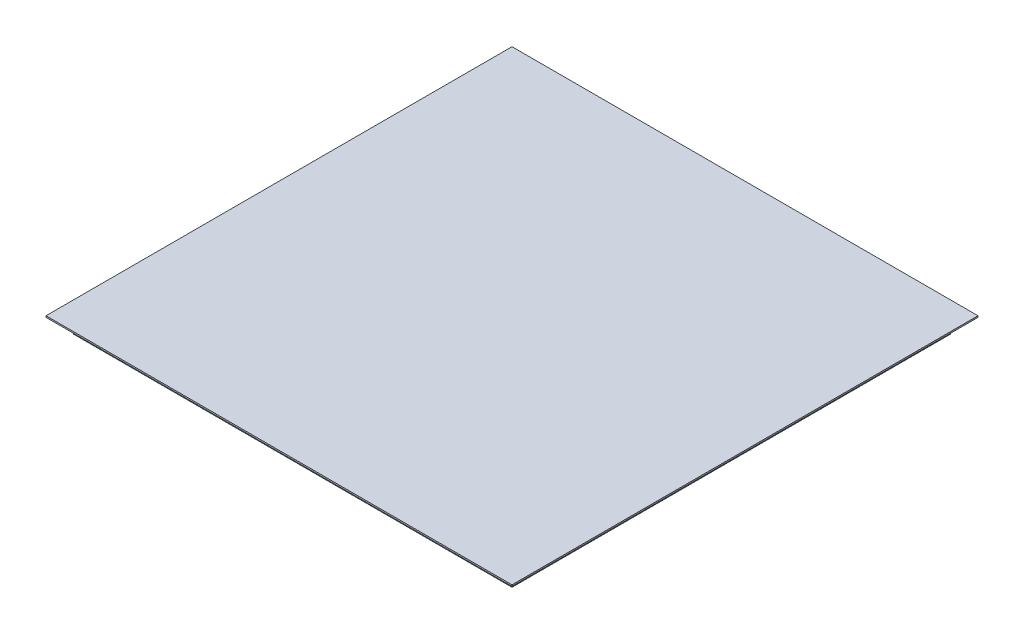
SolidWorks part; units mm, degrees
ref_plane "前视基准面" through (0, 0, 0) normal (0, 0, 1) x (1, 0, 0)
ref_plane "上视基准面" through (0, 0, 0) normal (0, 1, 0) x (1, 0, 0)
ref_plane "右视基准面" through (0, 0, 0) normal (1, 0, 0) x (0, 0, -1)
sketch "草图1" plane through (0, 0, 0) normal (0, 1, 0) x (1, 0, 0)
  line L1 (-320, -320) -> (320, -320)
  line L2 (-320, -320) -> (-320, 320)
  line L3 (-320, 320) -> (320, 320)
  line L4 (320, -320) -> (320, 320)
  line L5 (-320, -320) -> (320, 320) construction
  line L6 (-320, 320) -> (320, -320) construction
  point P0 (0, 0)
  dimension "D1" = 640
  dimension "D2" = 640
extrude "凸台-拉伸1" add sketch "草图1" along normal blind 2
sketch "草图2" plane through (0, 0, 0) normal (0, -1, 0) x (1, 0, 0)
  line L0 (299, 297.5858) -> (2.4142, 1)
  line L1 (-320, 0) -> (320, 0) construction
  line L2 (-320, -320) -> (-320, 320) construction
  line L3 (320, 320) -> (320, -320) construction
  line L4 (0, 320) -> (0, -320) construction
  line L5 (-320, 320) -> (320, 320) construction
  line L6 (320, -320) -> (-320, -320) construction
  line L7 (1, 1) -> (299, 1)
  line L8 (-300, -300) -> (300, -300) construction
  line L9 (-300, -300) -> (-300, 300) construction
  line L10 (-300, 300) -> (300, 300) construction
  line L11 (300, -300) -> (300, 300) construction
  line L12 (-300, -300) -> (300, 300) construction
  line L13 (-300, 300) -> (300, -300) construction
  line L16 (-299, 299) -> (299, 299)
  line L18 (-299, -299) -> (299, 299) construction
  line L19 (-299, 299) -> (299, -299) construction
  line L20 (-301, -301) -> (301, -301)
  line L21 (-301, -301) -> (-301, 301)
  line L22 (-301, 301) -> (301, 301)
  line L23 (301, -301) -> (301, 301)
  line L24 (-301, -301) -> (301, 301) construction
  line L25 (-301, 301) -> (301, -301) construction
  line L26 (1, -1) -> (299, -1)
  line L27 (1, -1) -> (1, -299)
  line L28 (-1, -1) -> (-1, -299)
  line L29 (-1, -1) -> (-299, -1)
  line L30 (-1, 1) -> (-299, 1)
  line L31 (-1, 1) -> (-1, 299)
  line L32 (1, 1) -> (1, 299)
  line L33 (297.5858, 299) -> (1, 2.4142)
  line L34 (297.5858, -299) -> (1, -2.4142)
  line L35 (299, -297.5858) -> (2.4142, -1)
  line L36 (-299, -297.5858) -> (-2.4142, -1)
  line L37 (-297.5858, -299) -> (-1, -2.4142)
  line L38 (-297.5858, 299) -> (-1, 2.4142)
  line L39 (-299, 297.5858) -> (-2.4142, 1)
  line L40 (-299, 299) -> (-299, -299)
  line L41 (299, 299) -> (299, -299)
  line L42 (299, -299) -> (-299, -299)
  point P12 (0, 0)
  point P17 (0, 0)
  point P22 (0, 0)
  point P46 (0, 0)
  point P59 (0, 0)
  dimension "D1" = 20
  dimension "D2" = 20
  dimension "D3" = 1
  dimension "D4" = 1
  dimension "D5" = 2
  dimension "D7" = 2
  dimension "D6" = 4
  dimension "D8" = 4
extrude "凸台-拉伸2" add sketch "草图2" along normal blind 20 contours L20 L23 L22 L21 L41 L42 L40 L16 | L42 L41 L35 L26 L27 L34 | L16 L40 L39 L30 L31 L38 | L42 L27 L26 L41 L7 L32 L16 L31 L30 L40 L29 L28 | L41 L16 L33 L32 L7 L0 | L42 L37 L28 L29 L36 L40 region at (150, 0, 150) region at (0, 0, 0) region at (150, 0, -150) region at (-150, 0, 150) region at (-150, 0, -150) region at (-300.1486, 0, 0)
sketch "草图3" plane through (0, 0, 0) normal (0, -1, 0) x (1, 0, 0)
  line L0 (301, 301) -> (-301, -301) construction
  line L2 (-30, -30) -> (30, -30)
  line L3 (-30, -30) -> (-30, 30)
  line L4 (-30, 30) -> (30, 30)
  line L5 (30, -30) -> (30, 30)
  line L6 (-30, -30) -> (30, 30) construction
  line L7 (-30, 30) -> (30, -30) construction
  point P2 (0, 0)
  dimension "D1" = 60
sketch "草图4" plane through (0, 0, 0) normal (0, -1, 0) x (1, 0, 0)
  line L0 (-30, 30) -> (30, -30) construction
  circle A0 centre (0, 0) radius 12.5
  dimension "D1" = 25
extrude "切除-拉伸1" cut sketch "草图4" along normal through all
ref_plane "基准面1" through (0, -5, 0) normal (0, -1, 0) x (-1, 0, 0)
extrude "切除-拉伸2" cut sketch "草图3" along normal blind 2 from surface starting at plane "基准面1"
extrude "凸台-拉伸3" add sketch "草图3<2>" along normal blind 2 from surface separate body starting at plane "基准面1"
sketch "草图3<2>" plane through (0, 0, 0) normal (0, -1, 0) x (1, 0, 0) same geometry as "草图3"
sketch "草图5" plane through (0, -7, 0) normal (0, -1, 0) x (1, 0, 0)
  line L0 (0, 0) -> (8.08, 0) construction
  circle A0 centre (8.08, 0) radius 1.6
  circle A1 centre (0, -8.08) radius 1.6
  circle A2 centre (-8.08, 0) radius 1.6
  circle A3 centre (0, 8.08) radius 1.6
  point P13 (0, 0)
  dimension "D1" = 3.2
  dimension "D2" = 8.08
  dimension "D3" = 4
extrude "切除-拉伸3" cut sketch "草图5" against normal up to next (2 mm away)
extrude "切除-拉伸4" cut sketch "草图3<3>" against normal offset from surface (8 mm away) 5 from surface up to face at (8.08, -7, -1.6) starting at face at (0, -20, 0)
sketch "草图3<3>" plane through (0, 0, 0) normal (0, -1, 0) x (1, 0, 0) same geometry as "草图3"
sketch "草图7" plane through (0, 0, -1) normal (0, 0, -1) x (-1, 0, 0)
  line L0 (30, -12) -> (50, -20)
  line L1 (50, -20) -> (30, -20)
  line L2 (0, 0) -> (0, -20) construction
  line L3 (301, -20) -> (-301, -20) construction
  line L4 (-30, -12) -> (-30, -20)
  line L5 (-50, -20) -> (-30, -20)
  line L6 (-30, -12) -> (-50, -20)
  line L10 (12.4599, -12) -> (30, -12)
  line L11 (30, -12) -> (30, -20)
  line L12 (30, -20) -> (299, -20)
  line L13 (299, -20) -> (299, 0)
  line L14 (299, 0) -> (12.4599, 0)
  line L15 (12.4599, 0) -> (12.4599, -5)
  line L16 (12.4599, -5) -> (30, -5)
  line L17 (30, -5) -> (30, -7)
  line L18 (30, -7) -> (12.4599, -7)
  line L19 (12.4599, -7) -> (12.4599, -12)
  line L20 (12.4599, -12) -> (30, -12)
  line L21 (30, -12) -> (30, -20)
  line L22 (30, -20) -> (299, -20)
  line L23 (299, -20) -> (299, 0)
  line L24 (299, 0) -> (12.4599, 0)
  line L25 (12.4599, 0) -> (12.4599, -5)
  line L26 (12.4599, -5) -> (30, -5)
  line L27 (30, -5) -> (30, -7)
  line L28 (30, -7) -> (12.4599, -7)
  line L29 (12.4599, -7) -> (12.4599, -12)
  line M15 (30, -12) -> (30, -20)
  line M16 (30, -20) -> (299, -20)
  dimension "D2" = 20
  dimension "D1" = 0
extrude "切除-拉伸5" cut sketch "草图7" against normal up to surface (2 mm away) contours L4 L6 L5 | L0 M15 M16 region at (-36.6667, -17.3333, -1) region at (36.6667, -17.3333, -1) up to face at (76.784, -8.8, 1)
sketch "草图8" plane through (0.7071, 0, 0.7071) normal (0.7071, 0, 0.7071) x (0.7071, 0, -0.7071)
  line L0 (41.4264, -12) -> (61.4264, -20)
  line L1 (61.4264, -20) -> (41.4264, -20)
  line L2 (0, 2) -> (0, -20) construction
  line L3 (-41.4264, -12) -> (-41.4264, -20)
  line L4 (-61.4264, -20) -> (-41.4264, -20)
  line L5 (-41.4264, -12) -> (-61.4264, -20)
  line L10 (41.4264, -12) -> (41.4264, -20)
  line L11 (41.4264, -20) -> (421.8499, -20)
  line L12 (421.8499, -20) -> (421.8499, 0)
  line L13 (421.8499, 0) -> (12.4599, 0)
  line L14 (12.4599, 0) -> (12.4599, -5)
  line L15 (12.4599, -5) -> (41.4264, -5)
  line L16 (41.4264, -5) -> (41.4264, -7)
  line L17 (41.4264, -7) -> (12.4599, -7)
  line L18 (12.4599, -7) -> (12.4599, -12)
  line L19 (12.4599, -12) -> (41.4264, -12)
  line L20 (41.4264, -12) -> (41.4264, -20)
  line L21 (41.4264, -20) -> (421.8499, -20)
  line L22 (421.8499, -20) -> (421.8499, 0)
  line L23 (421.8499, 0) -> (12.4599, 0)
  line L24 (12.4599, 0) -> (12.4599, -5)
  line L25 (12.4599, -5) -> (41.4264, -5)
  line L26 (41.4264, -5) -> (41.4264, -7)
  line L27 (41.4264, -7) -> (12.4599, -7)
  line L28 (12.4599, -7) -> (12.4599, -12)
  line L29 (12.4599, -12) -> (41.4264, -12)
  line M14 (41.4264, -12) -> (41.4264, -20)
  line M15 (41.4264, -20) -> (421.8499, -20)
  dimension "D2" = 20
  dimension "D1" = 0
extrude "切除-拉伸6" cut sketch "草图8" against normal up to surface (2 mm away) contours L3 L5 L4 | L0 M14 M15 region at (34.714, -17.3333, -33.2998) region at (-33.2998, -17.3333, 34.714) up to face at (-75.607, -8.8, 74.1928)
